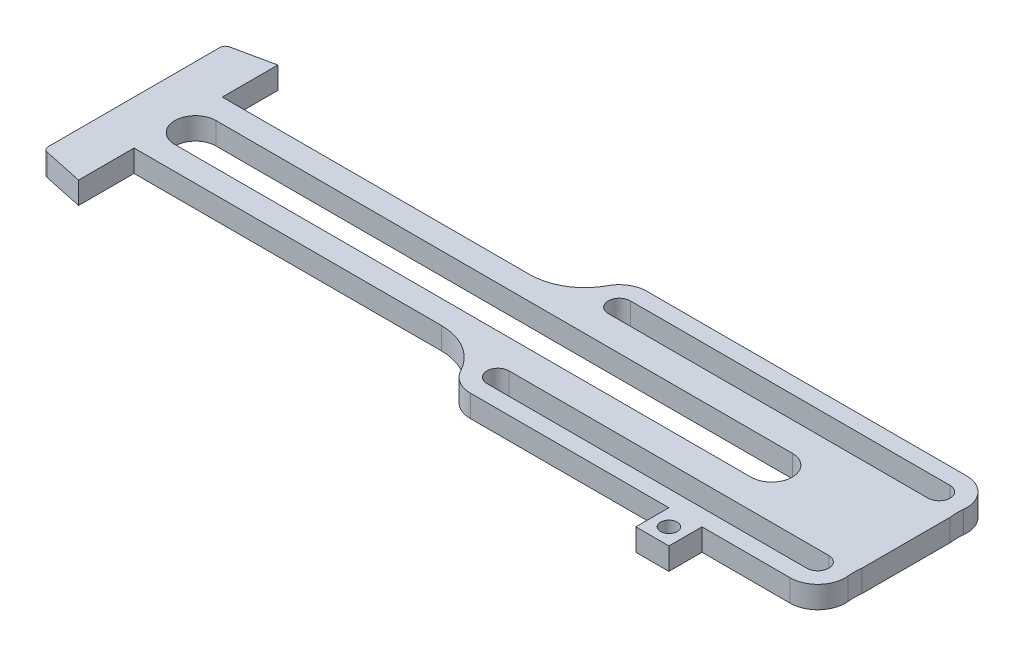
SolidWorks part; units mm, degrees
ref_plane "Спереди" through (0, 0, 0) normal (0, 0, 1) x (1, 0, 0)
ref_plane "Сверху" through (0, 0, 0) normal (0, 1, 0) x (1, 0, 0)
ref_plane "Справа" through (0, 0, 0) normal (1, 0, 0) x (0, 0, -1)
sketch "Эскиз1" plane through (0, 0, 0) normal (0, 1, 0) x (1, 0, 0)
  line L0 (0, 0) -> (-140, 0) construction
  line L1 (-140, -17) -> (-140, 17)
  line L2 (-140, 17) -> (-138, 19)
  line L3 (-138, 19) -> (-132, 19)
  line L4 (-132, 19) -> (-132, 8)
  line L5 (-132, 8) -> (0, 8)
  line L6 (0, 8) -> (0, -8)
  line L7 (-132, -8) -> (0, -8)
  line L8 (-132, -19) -> (-132, -8)
  line L9 (-138, -19) -> (-132, -19)
  line L10 (-140, -17) -> (-138, -19)
  line B0 (-128.9251, 3.8197) -> (-24.422, 3.8197) construction
  line B1 (-24.422, -3.6803) -> (-128.9251, -3.6803) construction
  line B2 (-139.9744, 15.5632) -> (-139.9744, -15.4163) construction
  line B3 (-139.1824, -16.3945) -> (-131.9744, -17.9266) construction
  line B4 (-131.9744, -7.9266) -> (-76.2409, -7.9266) construction
  line B5 (-76.2409, 8.0734) -> (-131.9744, 8.0734) construction
  line B6 (-139.1824, 16.5413) -> (-131.9744, 18.0734) construction
  arc B7 (-128.9251, 3.8197) -> (-128.9251, -3.6803) centre (-128.9251, 0.0697) ccw construction
  arc B8 (-139.1824, 16.5413) -> (-139.9744, 15.5632) centre (-138.9744, 15.5632) ccw construction
  dimension "D1" = 38
  dimension "D2" = 135
  dimension "D3" = 8
  dimension "D4" = 6
  dimension "D5" = 140
  dimension "D6" = 16
sketch_block_instance "Блок1-1"
sketch_block "Блок1"
extrude "Бобышка-Вытянуть1" add sketch "Эскиз1" along normal blind 4
sketch "Эскиз2" plane through (0, 0, 0) normal (0, -1, 0) x (1, 0, 0)
  line L0 (0, 0) -> (-174.855, 0) construction
  line L1 (-63, 11) -> (-5, 11) construction
  line L2 (-63, 13) -> (-5, 13)
  line L3 (-63, 9) -> (-5, 9)
  line L4 (-63, 11) -> (-5, 11) construction
  line L5 (-63, 16) -> (-5, 16)
  line L6 (-63, 6) -> (-5, 6)
  line L8 (-63, -11) -> (-5, -11) construction
  line L9 (-63, -13) -> (-5, -13)
  line L10 (-63, -9) -> (-5, -9)
  line L11 (-63, -11) -> (-5, -11) construction
  line L12 (-63, -16) -> (-5, -16)
  line L13 (-63, -6) -> (-5, -6)
  arc A0 (-63, 13) -> (-63, 9) centre (-63, 11) ccw
  arc A1 (-5, 9) -> (-5, 13) centre (-5, 11) ccw
  arc A2 (-63, 16) -> (-63, 6) centre (-63, 11) ccw
  arc A3 (-5, 6) -> (-5, 16) centre (-5, 11) ccw
  arc A4 (-63, -13) -> (-63, -9) centre (-63, -11) cw
  arc A5 (-5, -9) -> (-5, -13) centre (-5, -11) cw
  arc A6 (-63, -16) -> (-63, -6) centre (-63, -11) cw
  arc A7 (-5, -6) -> (-5, -16) centre (-5, -11) cw
  point P5 (-34, 11)
  point P11 (-34, 11)
  point P21 (-34, -11)
  point P28 (-34, -11)
  dimension "D1" = 4
  dimension "D2" = 10
  dimension "D3" = 58
  dimension "D4" = 22
  dimension "D5" = 5
extrude "Бобышка-Вытянуть2" add sketch "Эскиз2" against normal up to surface (4 mm away) up to face at (-108.4, 4, 0)
fillet "Скругление1" radius 10 4 edges at (-1, 2, 8) (-1, 2, -8) (-67, 2, -8) (-67, 2, 8)
sketch "Эскиз3" plane through (0, 0, 0) normal (0, -1, 0) x (1, 0, 0)
  line L0 (-24.3607, 3.7538) -> (-128.8637, 3.7538)
  line L1 (-128.8637, -3.7462) -> (-24.3607, -3.7462)
  line L2 (-24.3607, 1.5038) -> (-128.8637, 1.5038)
  line L3 (-128.8637, -1.4962) -> (-24.3607, -1.4962)
  line L4 (-24.3607, 1.5038) -> (-128.8637, 1.5038) construction
  line L5 (-128.8637, -1.4962) -> (-24.3607, -1.4962) construction
  arc A0 (-128.8637, 3.7538) -> (-128.8637, -3.7462) centre (-128.8637, 0.0038) ccw
  arc A1 (-24.3607, -3.7462) -> (-24.3607, 3.7538) centre (-24.3607, 0.0038) ccw
  arc A2 (-128.8637, 1.5038) -> (-128.8637, -1.4962) centre (-128.8637, 0.0038) ccw
  arc A3 (-24.3607, -1.4962) -> (-24.3607, 1.5038) centre (-24.3607, 0.0038) ccw
  arc A4 (-128.8637, 1.5038) -> (-128.8637, -1.4962) centre (-128.8637, 0.0038) ccw construction
  arc A5 (-24.3607, -1.4962) -> (-24.3607, 1.5038) centre (-24.3607, 0.0038) ccw construction
  dimension "D3" = 7.5
  dimension "D1" = 0
  dimension "D2" = 2.25
extrude "Вырез-Вытянуть1" cut sketch "Эскиз3" against normal through all
sketch "Эскиз4" plane through (0, 4, 0) normal (0, 1, 0) x (1, 0, 0)
  line L1 (-21, -22) -> (-27, -22)
  line L2 (-21, -22) -> (-21, -16)
  line L3 (-21, -16) -> (-27, -16)
  line L4 (-27, -22) -> (-27, -16)
  line L5 (-21, -22) -> (-27, -16) construction
  line L6 (-21, -16) -> (-27, -22) construction
  line L7 (-63, -16) -> (-5, -16) construction
  line L8 (0, -8) -> (0, 8) construction
  point P0 (-24, -19)
  dimension "D1" = 6
  dimension "D2" = 6
  dimension "D3" = 21
extrude "Бобышка-Вытянуть7" add sketch "Эскиз4" against normal blind 4
sketch "Эскиз6" plane through (0, 4, 0) normal (0, 1, 0) x (1, 0, 0)
  line L0 (-27, -16) -> (-21, -22) construction
  circle A0 centre (-24, -19) radius 1.5
  dimension "D1" = 3
extrude "Вырез-Вытянуть4" cut sketch "Эскиз6" against normal through all
sketch "Эскиз7" plane through (0, 4, 0) normal (0, 1, 0) x (1, 0, 0)
  line L1 (-140, 16.3675) -> (-131.9744, 18.0734)
  line L2 (-131.9744, 18.0734) -> (-132, 19)
  line L3 (-132, 19) -> (-138, 19)
  line L4 (-138, 19) -> (-140, 17)
  line L5 (-140, 17) -> (-140, 16.3675)
  line L6 (-140, -17) -> (-140, 17) construction
  line L7 (-139.1824, 16.5413) -> (-131.9744, 18.0734) construction
extrude "Вырез-Вытянуть5" cut sketch "Эскиз7" against normal through all
fillet "Скругление5" radius 1 1 edges at (-140, 2, -16.3675)
mirror "Зеркальное отражение5" about plane through (0, 0, 0) normal (0, 0, 1) of "Вырез-Вытянуть5"
fillet "Скругление6" radius 1 1 edges at (-140, 2, 16.3675)
